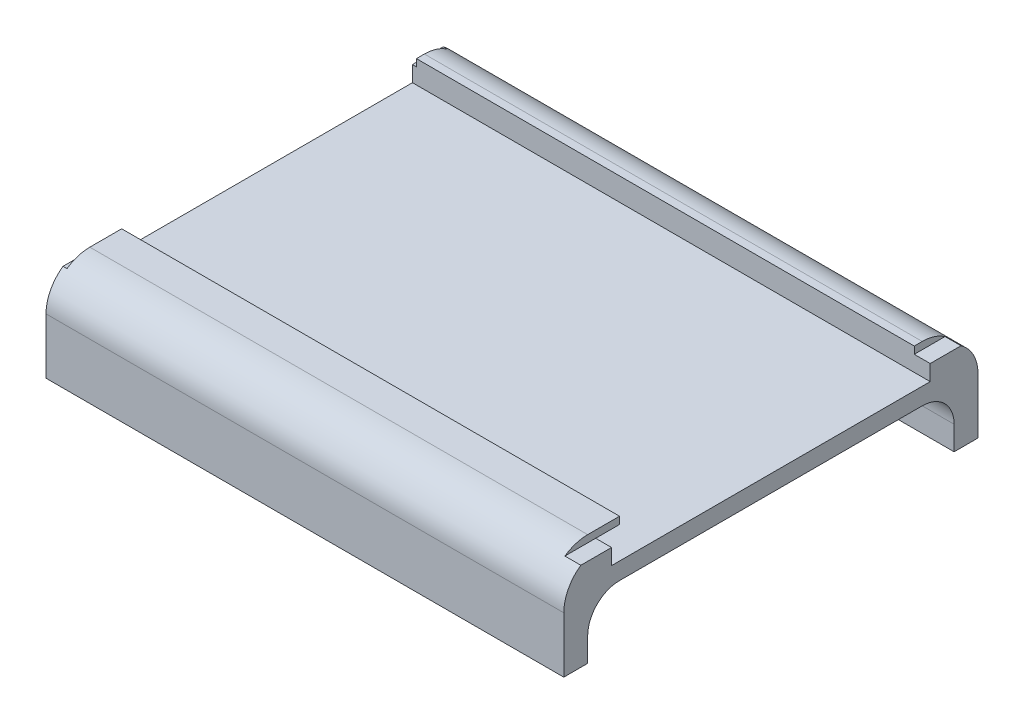
SolidWorks part; units mm, degrees
material "ABS"
ref_plane "Front Plane" through (0, 0, 0) normal (0, 0, 1) x (1, 0, 0)
ref_plane "Top Plane" through (0, 0, 0) normal (0, 1, 0) x (1, 0, 0)
ref_plane "Right Plane" through (0, 0, 0) normal (1, 0, 0) x (0, 0, -1)
sketch "Sketch1" plane through (0, 0, 0) normal (0, 1, 0) x (1, 0, 0)
  line L1 (0, 0) -> (165.1, 0)
  line L2 (0, 0) -> (0, 132.08)
  line L3 (0, 132.08) -> (165.1, 132.08)
  line L4 (165.1, 0) -> (165.1, 132.08)
  dimension "D1" = 132.08
  dimension "D2" = 165.1
extrude "Boss-Extrude1" add sketch "Sketch1" along normal blind 12.7
ref_plane "Plane1" through (0, 12.7, 0) normal (0, 1, 0) x (1, 0, 0)
sketch "Sketch2" plane through (0, 12.7, 0) normal (0, 1, 0) x (1, 0, 0)
  line L0 (0, 132.08) -> (0, 0) construction
  line L1 (0, 116.84) -> (165.1, 116.84)
  line L2 (0, 116.84) -> (0, 15.24)
  line L3 (0, 15.24) -> (165.1, 15.24)
  line L4 (165.1, 116.84) -> (165.1, 15.24)
  line L5 (165.1, 0) -> (165.1, 132.08) construction
  line L6 (165.1, 132.08) -> (0, 132.08) construction
  line L7 (0, 0) -> (165.1, 0) construction
  dimension "D1" = 15.24
  dimension "D2" = 15.24
extrude "Cut-Extrude1" cut sketch "Sketch2" against normal blind 7.286
sketch "Sketch3" plane through (0, 12.7, 0) normal (0, 1, 0) x (1, 0, 0)
  line L0 (165.1, 116.84) -> (0, 116.84) construction
  line L1 (0, 132.08) -> (1.27, 132.08)
  line L2 (0, 132.08) -> (0, 116.84)
  line L3 (0, 116.84) -> (1.27, 116.84)
  line L4 (1.27, 132.08) -> (1.27, 116.84)
  line L5 (0, 0) -> (165.1, 0) construction
  line L6 (165.1, 132.08) -> (160.02, 132.08)
  line L7 (165.1, 132.08) -> (165.1, 116.84)
  line L8 (165.1, 116.84) -> (160.02, 116.84)
  line L9 (160.02, 132.08) -> (160.02, 116.84)
  line L10 (165.1, 15.24) -> (160.02, 15.24)
  line L11 (165.1, 15.24) -> (165.1, 0)
  line L12 (165.1, 0) -> (160.02, 0)
  line L13 (160.02, 15.24) -> (160.02, 0)
  line L15 (0, 15.24) -> (1.27, 15.24)
  line L16 (0, 15.24) -> (0, 0)
  line L17 (0, 0) -> (1.27, 0)
  line L18 (1.27, 15.24) -> (1.27, 0)
  dimension "D1" = 1.27
  dimension "D2" = 5.08
extrude "Cut-Extrude2" cut sketch "Sketch3" against normal blind 2.286
sketch "Sketch5" plane through (0, 0, 0) normal (0, -1, 0) x (1, 0, 0)
  line L0 (0, -132.08) -> (0, 0) construction
  line L1 (165.1, -132.08) -> (0, -132.08)
  line L2 (165.1, -132.08) -> (165.1, -124.46)
  line L3 (165.1, -124.46) -> (0, -124.46)
  line L4 (0, -132.08) -> (0, -124.46)
  line L6 (165.1, 0) -> (0, 0)
  line L7 (165.1, 0) -> (165.1, -7.62)
  line L8 (165.1, -7.62) -> (0, -7.62)
  line L9 (0, 0) -> (0, -7.62)
  dimension "D1" = 7.62
  dimension "D2" = 7.62
extrude "Boss-Extrude3" add sketch "Sketch5" along normal blind 17.78
fillet "Fillet1" radius 12.7 2 edges at (80.645, 12.7, 0) (80.645, 12.7, -132.08)
fillet "Fillet2" radius 10.16 2 edges at (82.55, 0, -7.62) (82.55, 0, -124.46)
sketch "Sketch6" plane through (0, 0, -15.24) normal (0, 0, -1) x (-1, 0, 0)
  line L7 (-1.27, 10.414) -> (-160.02, 10.414)
  line L8 (-1.27, 10.414) -> (-1.27, 12.7)
  line L9 (-1.27, 12.7) -> (-160.02, 12.7)
  line L10 (-160.02, 10.414) -> (-160.02, 12.7)
extrude "Boss-Extrude5" add sketch "Sketch6" along normal blind 7.62
